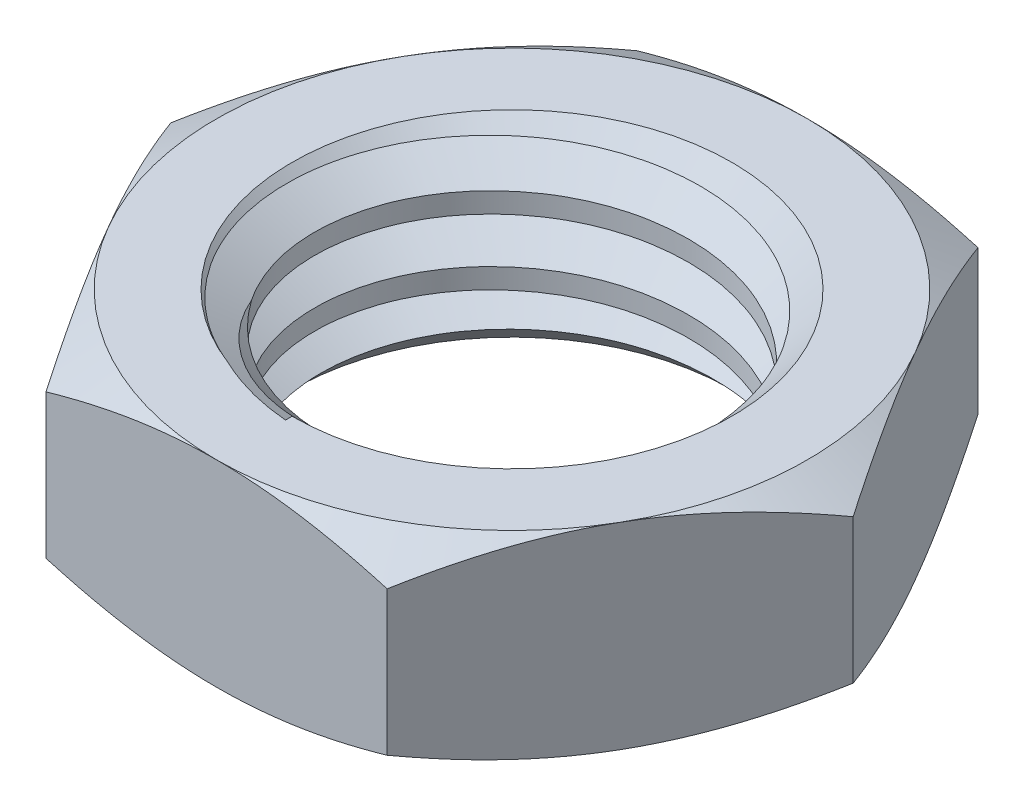
SolidWorks part; units mm, degrees
ref_plane "Plano frontal" through (0, 0, 0) normal (0, 0, 1) x (1, 0, 0)
ref_plane "Plano superior" through (0, 0, 0) normal (0, 1, 0) x (1, 0, 0)
ref_plane "Plano direito" through (0, 0, 0) normal (1, 0, 0) x (0, 0, -1)
sketch "Esboço2" plane through (0, 0, 0) normal (0, 1, 0) x (1, 0, 0)
  line L1 (10.3923, 0) -> (5.1962, 9)
  line L2 (5.1962, 9) -> (-5.1962, 9)
  line L3 (-5.1962, 9) -> (-10.3923, 0)
  line L4 (-10.3923, 0) -> (-5.1962, -9)
  line L5 (-5.1962, -9) -> (5.1962, -9)
  line L6 (5.1962, -9) -> (10.3923, 0)
  circle A0 centre (0, 0) radius 9 construction
  dimension "D1" = 18
extrude "Ressalto-extrusão2" add sketch "Esboço2" along normal mid plane 6
sketch "Esboço3" plane through (0, 3, 0) normal (0, 1, 0) x (1, 0, 0)
  line L0 (5.1962, -9) -> (10.3923, 0) construction
  circle A0 centre (0, 0) radius 9
extrude "Corte-extrusão1" cut sketch "Esboço3" against normal blind 8 draft 60 flip side to cut
mirror "Espelhar1" about plane through (0, 0, 0) normal (0, 1, 0) of "Corte-extrusão1"
sketch "Esboço4" plane through (0, 3, 0) normal (0, 1, 0) x (1, 0, 0)
  circle A0 centre (0, 0) radius 5.7
  dimension "D1" = 11.4
extrude "Corte-extrusão2" cut sketch "Esboço4" against normal blind 10 contours A0
chamfer "Chanfro2" distance 1 angle 45 2 edges at (0, -3, 5.7) (0, 3, 5.7)
sketch "Esboço5" plane through (0, 3, 0) normal (0, 1, 0) x (1, 0, 0)
  circle A0 centre (0, 0) radius 5.7 construction
  circle A1 centre (0, 0) radius 5.7
curve "Hélice/Espiral1" pitch 2 height 6 turns 3
sketch "Esboço6" plane through (0, 0, 0) normal (1, 0, 0) x (0, 0, -1)
  line L1 (-6.9, 3) -> (-5.1, 1.9608)
  line L2 (-5.1, 1.9608) -> (-5.1, 4.0392)
  line L3 (-5.1, 4.0392) -> (-6.9, 3)
  circle A0 centre (-5.7, 3) radius 0.6 construction
  point P1 (0, 0)
  dimension "D1" = 1.2
sweep "Varredura de corte1" cut profiles "Esboço6" path "Hélice/Espiral1"
